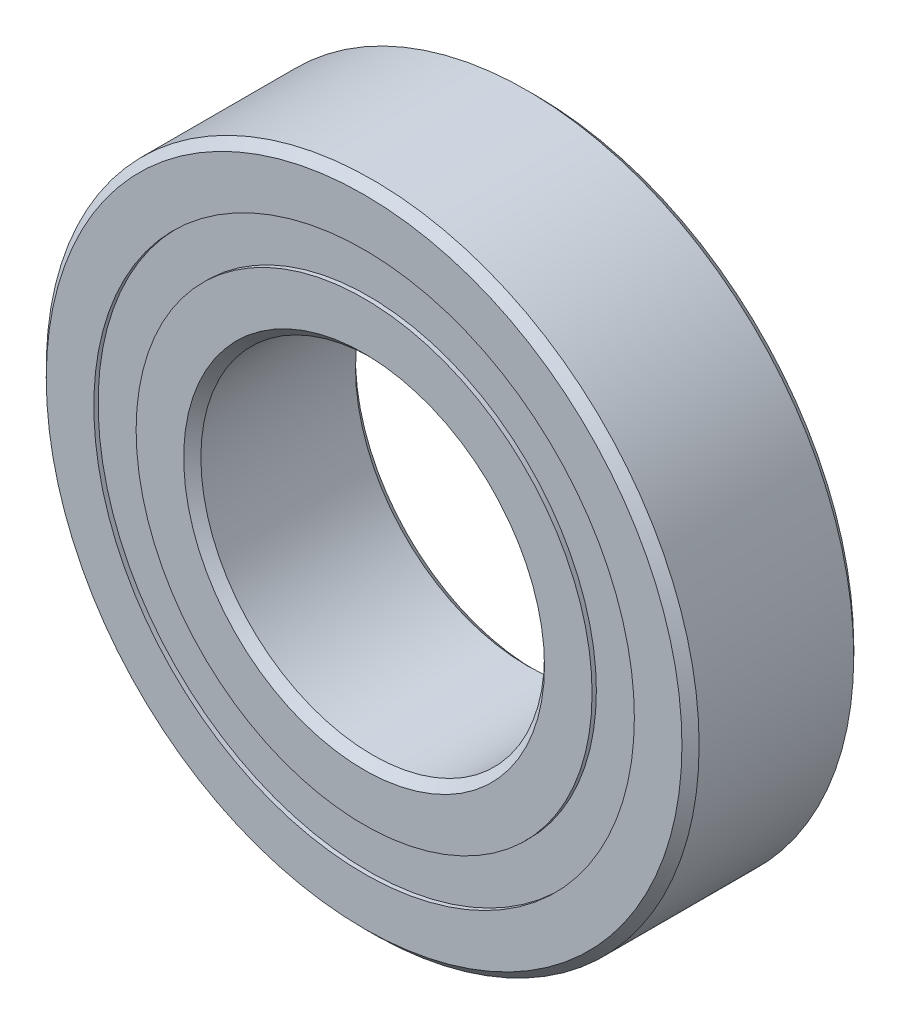
SolidWorks part; units mm, degrees
material "AISI 1020"
ref_plane "Front Plane" through (0, 0, 0) normal (0, 0, 1) x (1, 0, 0)
ref_plane "Top Plane" through (0, 0, 0) normal (0, 1, 0) x (1, 0, 0)
ref_plane "Right Plane" through (0, 0, 0) normal (1, 0, 0) x (0, 0, -1)
sketch "Sketch1" plane through (0, 0, 0) normal (1, 0, 0) x (0, 0, -1)
  line L0 (-2.5, 0) -> (2.5, 0) construction
  line L1 (0, 9.5) -> (0, -9.5) construction
  line L2 (2.25, 9.5) -> (-2.25, 9.5)
  line L3 (-2.25, 9.5) -> (-2.5, 9.25)
  line L4 (-2.5, 9.25) -> (-2.5, 7.8654)
  line L5 (-2.5, 7.8654) -> (-1.1111, 7.8654)
  line L6 (2.5, 7.8654) -> (1.1111, 7.8654)
  line L7 (2.5, 9.25) -> (2.5, 7.8654)
  line L8 (2.25, 9.5) -> (2.5, 9.25)
  line L9 (0, 9.5) -> (0, 7.25) construction
  line L10 (0, 7.25) -> (0, 5) construction
  arc A0 (-1.1111, 7.8654) -> (1.1111, 7.8654) centre (0, 7.25) cw
  point P14 (0, 5)
  dimension "Width" = 5
  dimension "OD" = 19
  dimension "D1" = 45
  dimension "D2" = 0.25
  dimension "Shaft Dia" = 10
  dimension "D3" = 2.2222
  dimension "D4" = 0.6154
revolve "Revolve1" add sketch "Sketch1" angle 360 about L0
sketch "Sketch3" plane through (0, 0, 0) normal (1, 0, 0) x (0, 0, -1)
  line L0 (-2.5, 6.6346) -> (-1.1111, 6.6346)
  line L1 (0, 9.5) -> (0, -9.5) construction
  line L2 (-2.5, 9.25) -> (-2.5, 7.8654) construction
  line L3 (-2.5, 6.6346) -> (-2.5, 5.25)
  line L4 (-2.25, 9.5) -> (-2.5, 9.25) construction
  line L5 (-2.5, 5.25) -> (-2.25, 5)
  line L6 (-2.25, 5) -> (2.25, 5)
  line L7 (2.25, 9.5) -> (2.25, -9.5) construction
  line L8 (2.25, 5) -> (2.5, 5.25)
  line L9 (2.5, -9.25) -> (2.5, 9.25) construction
  line L10 (2.5, 5.25) -> (2.5, 6.6346)
  line L11 (2.5, 6.6346) -> (1.1111, 6.6346)
  line L13 (2.25, 9.5) -> (2.5, 9.25) construction
  arc A0 (1.1111, 7.8654) -> (-1.1111, 7.8654) centre (0, 7.25) ccw construction
  arc A1 (1.1111, 6.6346) -> (-1.1111, 6.6346) centre (0, 7.25) cw
revolve "Revolve3" add sketch "Sketch3" angle 360 about L0
sketch "Sketch4" plane through (0, 0, 0) normal (1, 0, 0) x (0, 0, -1)
  line L0 (-1.2701, 7.25) -> (1.2701, 7.25)
  arc A2 (-1.2701, 7.25) -> (1.2701, 7.25) centre (0, 7.25) cw
  arc A3 (1.1111, 7.8654) -> (-1.1111, 7.8654) centre (0, 7.25) ccw construction
revolve "Revolve4" add sketch "Sketch4" angle 360 about L0
ref_axis "Axis1" through (0, 0, -2.5) along (0, 0, 1)
pattern_circular "CirPattern1" count 12 every 30 about axis through (0, 0, -2.5) along (0, 0, 1) of bodies 104
sketch "Sketch5" plane through (0, 0, 0) normal (1, 0, 0) x (0, 0, -1)
  line L0 (-2.5, 7.8654) -> (-1.1111, 7.8654) construction
  line L1 (-2.375, 7.8654) -> (-1.2701, 7.8654)
  line L2 (-2.375, 7.8654) -> (-2.375, 6.6346)
  line L3 (-2.375, 6.6346) -> (-1.2701, 6.6346)
  line L4 (-1.2701, 7.8654) -> (-1.2701, 6.6346)
  line L5 (-2.5, 6.6346) -> (-1.1111, 6.6346) construction
  line L6 (2.5, 7.8654) -> (1.1111, 7.8654) construction
  line L7 (2.375, 7.8654) -> (1.2701, 7.8654)
  line L8 (2.375, 7.8654) -> (2.375, 6.6346)
  line L9 (2.375, 6.6346) -> (1.2701, 6.6346)
  line L10 (1.2701, 7.8654) -> (1.2701, 6.6346)
  line L11 (2.5, 6.6346) -> (1.1111, 6.6346) construction
  line L12 (-2.25, 9.5) -> (-2.5, 9.25) construction
  point P18 (-2.375, 9.375)
revolve "Revolve5" add sketch "Sketch5" angle 360 about L0
equation "\"D2@Sketch1\" = \"Width@Sketch1\"*.05"
equation "\"D3@Sketch1\" = \"Width@Sketch1\"/2.25"
equation "\"D4@Sketch1\" = (((\"OD@Sketch1\"-\"Width@Sketch1\")/2)/3.25)/3.5"
equation "\"D2@CirPattern1\" = 360/\"Balls@CirPattern1\""
